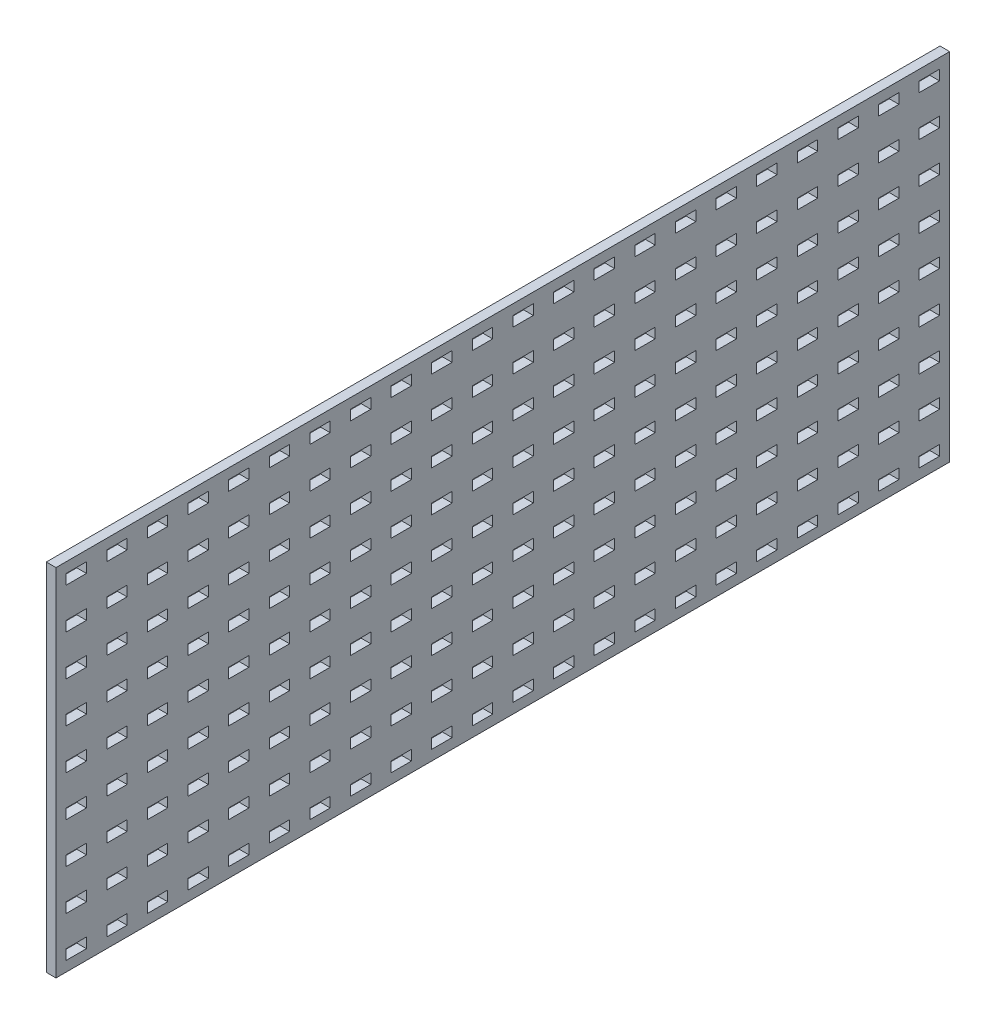
SolidWorks part; units mm, degrees
ref_plane "Front Plane" through (0, 0, 0) normal (0, 0, 1) x (1, 0, 0)
ref_plane "Top Plane" through (0, 0, 0) normal (0, 1, 0) x (1, 0, 0)
ref_plane "Right Plane" through (0, 0, 0) normal (1, 0, 0) x (0, 0, -1)
sketch "Sketch1" plane through (0, 0, 0) normal (1, 0, 0) x (0, 0, -1)
  line L1 (-279.4, -111.125) -> (279.4, -111.125)
  line L2 (-279.4, -111.125) -> (-279.4, 111.125)
  line L3 (-279.4, 111.125) -> (279.4, 111.125)
  line L4 (279.4, -111.125) -> (279.4, 111.125)
  line L5 (-279.4, -111.125) -> (279.4, 111.125) construction
  line L6 (-279.4, 111.125) -> (279.4, -111.125) construction
  point P0 (0, 0)
  dimension "D1" = 558.8
  dimension "D2" = 222.25
extrude "Boss-Extrude1" add sketch "Sketch1" along normal mid plane 6.0452
sketch "Sketch2" plane through (3.0226, 0, 0) normal (1, 0, 0) x (0, 0, -1)
  line L0 (-279.4, -111.125) -> (279.4, -111.125) construction
  line L1 (260.35, -98.425) -> (273.05, -98.425)
  line L2 (260.35, -98.425) -> (260.35, -104.775)
  line L3 (260.35, -104.775) -> (273.05, -104.775)
  line L4 (273.05, -98.425) -> (273.05, -104.775)
  line L5 (260.35, -98.425) -> (273.05, -104.775) construction
  line L6 (260.35, -104.775) -> (273.05, -98.425) construction
  line L7 (279.4, -111.125) -> (279.4, 111.125) construction
  line L8 (234.95, -104.775) -> (247.65, -104.775)
  line L9 (234.95, -98.425) -> (234.95, -104.775)
  line L10 (234.95, -98.425) -> (247.65, -98.425)
  line L11 (247.65, -98.425) -> (247.65, -104.775)
  line L12 (209.55, -104.775) -> (222.25, -104.775)
  line L13 (209.55, -98.425) -> (209.55, -104.775)
  line L14 (209.55, -98.425) -> (222.25, -98.425)
  line L15 (222.25, -98.425) -> (222.25, -104.775)
  line L16 (184.15, -104.775) -> (196.85, -104.775)
  line L17 (184.15, -98.425) -> (184.15, -104.775)
  line L18 (184.15, -98.425) -> (196.85, -98.425)
  line L19 (196.85, -98.425) -> (196.85, -104.775)
  line L20 (158.75, -104.775) -> (171.45, -104.775)
  line L21 (158.75, -98.425) -> (158.75, -104.775)
  line L22 (158.75, -98.425) -> (171.45, -98.425)
  line L23 (171.45, -98.425) -> (171.45, -104.775)
  line L24 (133.35, -104.775) -> (146.05, -104.775)
  line L25 (133.35, -98.425) -> (133.35, -104.775)
  line L26 (133.35, -98.425) -> (146.05, -98.425)
  line L27 (146.05, -98.425) -> (146.05, -104.775)
  line L28 (107.95, -104.775) -> (120.65, -104.775)
  line L29 (107.95, -98.425) -> (107.95, -104.775)
  line L30 (107.95, -98.425) -> (120.65, -98.425)
  line L31 (120.65, -98.425) -> (120.65, -104.775)
  line L32 (82.55, -104.775) -> (95.25, -104.775)
  line L33 (82.55, -98.425) -> (82.55, -104.775)
  line L34 (82.55, -98.425) -> (95.25, -98.425)
  line L35 (95.25, -98.425) -> (95.25, -104.775)
  line L36 (57.15, -104.775) -> (69.85, -104.775)
  line L37 (57.15, -98.425) -> (57.15, -104.775)
  line L38 (57.15, -98.425) -> (69.85, -98.425)
  line L39 (69.85, -98.425) -> (69.85, -104.775)
  line L40 (31.75, -104.775) -> (44.45, -104.775)
  line L41 (31.75, -98.425) -> (31.75, -104.775)
  line L42 (31.75, -98.425) -> (44.45, -98.425)
  line L43 (44.45, -98.425) -> (44.45, -104.775)
  line L44 (6.35, -104.775) -> (19.05, -104.775)
  line L45 (6.35, -98.425) -> (6.35, -104.775)
  line L46 (6.35, -98.425) -> (19.05, -98.425)
  line L47 (19.05, -98.425) -> (19.05, -104.775)
  line L48 (-19.05, -104.775) -> (-6.35, -104.775)
  line L49 (-19.05, -98.425) -> (-19.05, -104.775)
  line L50 (-19.05, -98.425) -> (-6.35, -98.425)
  line L51 (-6.35, -98.425) -> (-6.35, -104.775)
  line L52 (-44.45, -104.775) -> (-31.75, -104.775)
  line L53 (-44.45, -98.425) -> (-44.45, -104.775)
  line L54 (-44.45, -98.425) -> (-31.75, -98.425)
  line L55 (-31.75, -98.425) -> (-31.75, -104.775)
  line L56 (-69.85, -104.775) -> (-57.15, -104.775)
  line L57 (-69.85, -98.425) -> (-69.85, -104.775)
  line L58 (-69.85, -98.425) -> (-57.15, -98.425)
  line L59 (-57.15, -98.425) -> (-57.15, -104.775)
  line L60 (-95.25, -104.775) -> (-82.55, -104.775)
  line L61 (-95.25, -98.425) -> (-95.25, -104.775)
  line L62 (-95.25, -98.425) -> (-82.55, -98.425)
  line L63 (-82.55, -98.425) -> (-82.55, -104.775)
  line L64 (-120.65, -104.775) -> (-107.95, -104.775)
  line L65 (-120.65, -98.425) -> (-120.65, -104.775)
  line L66 (-120.65, -98.425) -> (-107.95, -98.425)
  line L67 (-107.95, -98.425) -> (-107.95, -104.775)
  line L68 (-146.05, -104.775) -> (-133.35, -104.775)
  line L69 (-146.05, -98.425) -> (-146.05, -104.775)
  line L70 (-146.05, -98.425) -> (-133.35, -98.425)
  line L71 (-133.35, -98.425) -> (-133.35, -104.775)
  line L72 (-171.45, -104.775) -> (-158.75, -104.775)
  line L73 (-171.45, -98.425) -> (-171.45, -104.775)
  line L74 (-171.45, -98.425) -> (-158.75, -98.425)
  line L75 (-158.75, -98.425) -> (-158.75, -104.775)
  line L76 (-196.85, -104.775) -> (-184.15, -104.775)
  line L77 (-196.85, -98.425) -> (-196.85, -104.775)
  line L78 (-196.85, -98.425) -> (-184.15, -98.425)
  line L79 (-184.15, -98.425) -> (-184.15, -104.775)
  line L80 (-222.25, -104.775) -> (-209.55, -104.775)
  line L81 (-222.25, -98.425) -> (-222.25, -104.775)
  line L82 (-222.25, -98.425) -> (-209.55, -98.425)
  line L83 (-209.55, -98.425) -> (-209.55, -104.775)
  line L84 (-247.65, -104.775) -> (-234.95, -104.775)
  line L85 (-247.65, -98.425) -> (-247.65, -104.775)
  line L86 (-247.65, -98.425) -> (-234.95, -98.425)
  line L87 (-234.95, -98.425) -> (-234.95, -104.775)
  line L88 (-273.05, -104.775) -> (-260.35, -104.775)
  line L89 (-273.05, -98.425) -> (-273.05, -104.775)
  line L90 (-273.05, -98.425) -> (-260.35, -98.425)
  line L91 (-260.35, -98.425) -> (-260.35, -104.775)
  line L92 (234.95, -79.375) -> (247.65, -79.375)
  line L93 (234.95, -73.025) -> (234.95, -79.375)
  line L94 (234.95, -73.025) -> (247.65, -73.025)
  line L95 (247.65, -73.025) -> (247.65, -79.375)
  line L96 (209.55, -79.375) -> (222.25, -79.375)
  line L97 (209.55, -73.025) -> (209.55, -79.375)
  line L98 (209.55, -73.025) -> (222.25, -73.025)
  line L99 (222.25, -73.025) -> (222.25, -79.375)
  line L100 (184.15, -79.375) -> (196.85, -79.375)
  line L101 (184.15, -73.025) -> (184.15, -79.375)
  line L102 (184.15, -73.025) -> (196.85, -73.025)
  line L103 (196.85, -73.025) -> (196.85, -79.375)
  line L104 (158.75, -79.375) -> (171.45, -79.375)
  line L105 (158.75, -73.025) -> (158.75, -79.375)
  line L106 (158.75, -73.025) -> (171.45, -73.025)
  line L107 (171.45, -73.025) -> (171.45, -79.375)
  line L108 (133.35, -79.375) -> (146.05, -79.375)
  line L109 (133.35, -73.025) -> (133.35, -79.375)
  line L110 (133.35, -73.025) -> (146.05, -73.025)
  line L111 (146.05, -73.025) -> (146.05, -79.375)
  line L112 (107.95, -79.375) -> (120.65, -79.375)
  line L113 (107.95, -73.025) -> (107.95, -79.375)
  line L114 (107.95, -73.025) -> (120.65, -73.025)
  line L115 (120.65, -73.025) -> (120.65, -79.375)
  line L116 (82.55, -79.375) -> (95.25, -79.375)
  line L117 (82.55, -73.025) -> (82.55, -79.375)
  line L118 (82.55, -73.025) -> (95.25, -73.025)
  line L119 (95.25, -73.025) -> (95.25, -79.375)
  line L120 (57.15, -79.375) -> (69.85, -79.375)
  line L121 (57.15, -73.025) -> (57.15, -79.375)
  line L122 (57.15, -73.025) -> (69.85, -73.025)
  line L123 (69.85, -73.025) -> (69.85, -79.375)
  line L124 (31.75, -79.375) -> (44.45, -79.375)
  line L125 (31.75, -73.025) -> (31.75, -79.375)
  line L126 (31.75, -73.025) -> (44.45, -73.025)
  line L127 (44.45, -73.025) -> (44.45, -79.375)
  line L128 (6.35, -79.375) -> (19.05, -79.375)
  line L129 (6.35, -73.025) -> (6.35, -79.375)
  line L130 (6.35, -73.025) -> (19.05, -73.025)
  line L131 (19.05, -73.025) -> (19.05, -79.375)
  line L132 (-19.05, -79.375) -> (-6.35, -79.375)
  line L133 (-19.05, -73.025) -> (-19.05, -79.375)
  line L134 (-19.05, -73.025) -> (-6.35, -73.025)
  line L135 (-6.35, -73.025) -> (-6.35, -79.375)
  line L136 (-44.45, -79.375) -> (-31.75, -79.375)
  line L137 (-44.45, -73.025) -> (-44.45, -79.375)
  line L138 (-44.45, -73.025) -> (-31.75, -73.025)
  line L139 (-31.75, -73.025) -> (-31.75, -79.375)
  line L140 (-69.85, -79.375) -> (-57.15, -79.375)
  line L141 (-69.85, -73.025) -> (-69.85, -79.375)
  line L142 (-69.85, -73.025) -> (-57.15, -73.025)
  line L143 (-57.15, -73.025) -> (-57.15, -79.375)
  line L144 (-95.25, -79.375) -> (-82.55, -79.375)
  line L145 (-95.25, -73.025) -> (-95.25, -79.375)
  line L146 (-95.25, -73.025) -> (-82.55, -73.025)
  line L147 (-82.55, -73.025) -> (-82.55, -79.375)
  line L148 (-120.65, -79.375) -> (-107.95, -79.375)
  line L149 (-120.65, -73.025) -> (-120.65, -79.375)
  line L150 (-120.65, -73.025) -> (-107.95, -73.025)
  line L151 (-107.95, -73.025) -> (-107.95, -79.375)
  line L152 (-146.05, -79.375) -> (-133.35, -79.375)
  line L153 (-146.05, -73.025) -> (-146.05, -79.375)
  line L154 (-146.05, -73.025) -> (-133.35, -73.025)
  line L155 (-133.35, -73.025) -> (-133.35, -79.375)
  line L156 (-171.45, -79.375) -> (-158.75, -79.375)
  line L157 (-171.45, -73.025) -> (-171.45, -79.375)
  line L158 (-171.45, -73.025) -> (-158.75, -73.025)
  line L159 (-158.75, -73.025) -> (-158.75, -79.375)
  line L160 (-196.85, -79.375) -> (-184.15, -79.375)
  line L161 (-196.85, -73.025) -> (-196.85, -79.375)
  line L162 (-196.85, -73.025) -> (-184.15, -73.025)
  line L163 (-184.15, -73.025) -> (-184.15, -79.375)
  line L164 (-222.25, -79.375) -> (-209.55, -79.375)
  line L165 (-222.25, -73.025) -> (-222.25, -79.375)
  line L166 (-222.25, -73.025) -> (-209.55, -73.025)
  line L167 (-209.55, -73.025) -> (-209.55, -79.375)
  line L168 (-247.65, -79.375) -> (-234.95, -79.375)
  line L169 (-247.65, -73.025) -> (-247.65, -79.375)
  line L170 (-247.65, -73.025) -> (-234.95, -73.025)
  line L171 (-234.95, -73.025) -> (-234.95, -79.375)
  line L172 (-273.05, -79.375) -> (-260.35, -79.375)
  line L173 (-273.05, -73.025) -> (-273.05, -79.375)
  line L174 (-273.05, -73.025) -> (-260.35, -73.025)
  line L175 (-260.35, -73.025) -> (-260.35, -79.375)
  line L176 (234.95, -53.975) -> (247.65, -53.975)
  line L177 (234.95, -47.625) -> (234.95, -53.975)
  line L178 (234.95, -47.625) -> (247.65, -47.625)
  line L179 (247.65, -47.625) -> (247.65, -53.975)
  line L180 (209.55, -53.975) -> (222.25, -53.975)
  line L181 (209.55, -47.625) -> (209.55, -53.975)
  line L182 (209.55, -47.625) -> (222.25, -47.625)
  line L183 (222.25, -47.625) -> (222.25, -53.975)
  line L184 (184.15, -53.975) -> (196.85, -53.975)
  line L185 (184.15, -47.625) -> (184.15, -53.975)
  line L186 (184.15, -47.625) -> (196.85, -47.625)
  line L187 (196.85, -47.625) -> (196.85, -53.975)
  line L188 (158.75, -53.975) -> (171.45, -53.975)
  line L189 (158.75, -47.625) -> (158.75, -53.975)
  line L190 (158.75, -47.625) -> (171.45, -47.625)
  line L191 (171.45, -47.625) -> (171.45, -53.975)
  line L192 (133.35, -53.975) -> (146.05, -53.975)
  line L193 (133.35, -47.625) -> (133.35, -53.975)
  line L194 (133.35, -47.625) -> (146.05, -47.625)
  line L195 (146.05, -47.625) -> (146.05, -53.975)
  line L196 (107.95, -53.975) -> (120.65, -53.975)
  line L197 (107.95, -47.625) -> (107.95, -53.975)
  line L198 (107.95, -47.625) -> (120.65, -47.625)
  line L199 (120.65, -47.625) -> (120.65, -53.975)
  line L200 (82.55, -53.975) -> (95.25, -53.975)
  line L201 (82.55, -47.625) -> (82.55, -53.975)
  line L202 (82.55, -47.625) -> (95.25, -47.625)
  line L203 (95.25, -47.625) -> (95.25, -53.975)
  line L204 (57.15, -53.975) -> (69.85, -53.975)
  line L205 (57.15, -47.625) -> (57.15, -53.975)
  line L206 (57.15, -47.625) -> (69.85, -47.625)
  line L207 (69.85, -47.625) -> (69.85, -53.975)
  line L208 (31.75, -53.975) -> (44.45, -53.975)
  line L209 (31.75, -47.625) -> (31.75, -53.975)
  line L210 (31.75, -47.625) -> (44.45, -47.625)
  line L211 (44.45, -47.625) -> (44.45, -53.975)
  line L212 (6.35, -53.975) -> (19.05, -53.975)
  line L213 (6.35, -47.625) -> (6.35, -53.975)
  line L214 (6.35, -47.625) -> (19.05, -47.625)
  line L215 (19.05, -47.625) -> (19.05, -53.975)
  line L216 (-19.05, -53.975) -> (-6.35, -53.975)
  line L217 (-19.05, -47.625) -> (-19.05, -53.975)
  line L218 (-19.05, -47.625) -> (-6.35, -47.625)
  line L219 (-6.35, -47.625) -> (-6.35, -53.975)
  line L220 (-44.45, -53.975) -> (-31.75, -53.975)
  line L221 (-44.45, -47.625) -> (-44.45, -53.975)
  line L222 (-44.45, -47.625) -> (-31.75, -47.625)
  line L223 (-31.75, -47.625) -> (-31.75, -53.975)
  line L224 (-69.85, -53.975) -> (-57.15, -53.975)
  line L225 (-69.85, -47.625) -> (-69.85, -53.975)
  line L226 (-69.85, -47.625) -> (-57.15, -47.625)
  line L227 (-57.15, -47.625) -> (-57.15, -53.975)
  line L228 (-95.25, -53.975) -> (-82.55, -53.975)
  line L229 (-95.25, -47.625) -> (-95.25, -53.975)
  line L230 (-95.25, -47.625) -> (-82.55, -47.625)
  line L231 (-82.55, -47.625) -> (-82.55, -53.975)
  line L232 (-120.65, -53.975) -> (-107.95, -53.975)
  line L233 (-120.65, -47.625) -> (-120.65, -53.975)
  line L234 (-120.65, -47.625) -> (-107.95, -47.625)
  line L235 (-107.95, -47.625) -> (-107.95, -53.975)
  line L236 (-146.05, -53.975) -> (-133.35, -53.975)
  line L237 (-146.05, -47.625) -> (-146.05, -53.975)
  line L238 (-146.05, -47.625) -> (-133.35, -47.625)
  line L239 (-133.35, -47.625) -> (-133.35, -53.975)
  line L240 (-171.45, -53.975) -> (-158.75, -53.975)
  line L241 (-171.45, -47.625) -> (-171.45, -53.975)
  line L242 (-171.45, -47.625) -> (-158.75, -47.625)
  line L243 (-158.75, -47.625) -> (-158.75, -53.975)
  line L244 (-196.85, -53.975) -> (-184.15, -53.975)
  line L245 (-196.85, -47.625) -> (-196.85, -53.975)
  line L246 (-196.85, -47.625) -> (-184.15, -47.625)
  line L247 (-184.15, -47.625) -> (-184.15, -53.975)
  line L248 (-222.25, -53.975) -> (-209.55, -53.975)
  line L249 (-222.25, -47.625) -> (-222.25, -53.975)
  line L250 (-222.25, -47.625) -> (-209.55, -47.625)
  line L251 (-209.55, -47.625) -> (-209.55, -53.975)
  line L252 (-247.65, -53.975) -> (-234.95, -53.975)
  line L253 (-247.65, -47.625) -> (-247.65, -53.975)
  line L254 (-247.65, -47.625) -> (-234.95, -47.625)
  line L255 (-234.95, -47.625) -> (-234.95, -53.975)
  line L256 (-273.05, -53.975) -> (-260.35, -53.975)
  line L257 (-273.05, -47.625) -> (-273.05, -53.975)
  line L258 (-273.05, -47.625) -> (-260.35, -47.625)
  line L259 (-260.35, -47.625) -> (-260.35, -53.975)
  line L260 (234.95, -28.575) -> (247.65, -28.575)
  line L261 (234.95, -22.225) -> (234.95, -28.575)
  line L262 (234.95, -22.225) -> (247.65, -22.225)
  line L263 (247.65, -22.225) -> (247.65, -28.575)
  line L264 (209.55, -28.575) -> (222.25, -28.575)
  line L265 (209.55, -22.225) -> (209.55, -28.575)
  line L266 (209.55, -22.225) -> (222.25, -22.225)
  line L267 (222.25, -22.225) -> (222.25, -28.575)
  line L268 (184.15, -28.575) -> (196.85, -28.575)
  line L269 (184.15, -22.225) -> (184.15, -28.575)
  line L270 (184.15, -22.225) -> (196.85, -22.225)
  line L271 (196.85, -22.225) -> (196.85, -28.575)
  line L272 (158.75, -28.575) -> (171.45, -28.575)
  line L273 (158.75, -22.225) -> (158.75, -28.575)
  line L274 (158.75, -22.225) -> (171.45, -22.225)
  line L275 (171.45, -22.225) -> (171.45, -28.575)
  line L276 (133.35, -28.575) -> (146.05, -28.575)
  line L277 (133.35, -22.225) -> (133.35, -28.575)
  line L278 (133.35, -22.225) -> (146.05, -22.225)
  line L279 (146.05, -22.225) -> (146.05, -28.575)
  line L280 (107.95, -28.575) -> (120.65, -28.575)
  line L281 (107.95, -22.225) -> (107.95, -28.575)
  line L282 (107.95, -22.225) -> (120.65, -22.225)
  line L283 (120.65, -22.225) -> (120.65, -28.575)
  line L284 (82.55, -28.575) -> (95.25, -28.575)
  line L285 (82.55, -22.225) -> (82.55, -28.575)
  line L286 (82.55, -22.225) -> (95.25, -22.225)
  line L287 (95.25, -22.225) -> (95.25, -28.575)
  line L288 (57.15, -28.575) -> (69.85, -28.575)
  line L289 (57.15, -22.225) -> (57.15, -28.575)
  line L290 (57.15, -22.225) -> (69.85, -22.225)
  line L291 (69.85, -22.225) -> (69.85, -28.575)
  line L292 (31.75, -28.575) -> (44.45, -28.575)
  line L293 (31.75, -22.225) -> (31.75, -28.575)
  line L294 (31.75, -22.225) -> (44.45, -22.225)
  line L295 (44.45, -22.225) -> (44.45, -28.575)
  line L296 (6.35, -28.575) -> (19.05, -28.575)
  line L297 (6.35, -22.225) -> (6.35, -28.575)
  line L298 (6.35, -22.225) -> (19.05, -22.225)
  line L299 (19.05, -22.225) -> (19.05, -28.575)
  line L300 (-19.05, -28.575) -> (-6.35, -28.575)
  line L301 (-19.05, -22.225) -> (-19.05, -28.575)
  line L302 (-19.05, -22.225) -> (-6.35, -22.225)
  line L303 (-6.35, -22.225) -> (-6.35, -28.575)
  line L304 (-44.45, -28.575) -> (-31.75, -28.575)
  line L305 (-44.45, -22.225) -> (-44.45, -28.575)
  line L306 (-44.45, -22.225) -> (-31.75, -22.225)
  line L307 (-31.75, -22.225) -> (-31.75, -28.575)
  line L308 (-69.85, -28.575) -> (-57.15, -28.575)
  line L309 (-69.85, -22.225) -> (-69.85, -28.575)
  line L310 (-69.85, -22.225) -> (-57.15, -22.225)
  line L311 (-57.15, -22.225) -> (-57.15, -28.575)
  line L312 (-95.25, -28.575) -> (-82.55, -28.575)
  line L313 (-95.25, -22.225) -> (-95.25, -28.575)
  line L314 (-95.25, -22.225) -> (-82.55, -22.225)
  line L315 (-82.55, -22.225) -> (-82.55, -28.575)
  line L316 (-120.65, -28.575) -> (-107.95, -28.575)
  line L317 (-120.65, -22.225) -> (-120.65, -28.575)
  line L318 (-120.65, -22.225) -> (-107.95, -22.225)
  line L319 (-107.95, -22.225) -> (-107.95, -28.575)
  line L320 (-146.05, -28.575) -> (-133.35, -28.575)
  line L321 (-146.05, -22.225) -> (-146.05, -28.575)
  line L322 (-146.05, -22.225) -> (-133.35, -22.225)
  line L323 (-133.35, -22.225) -> (-133.35, -28.575)
  line L324 (-171.45, -28.575) -> (-158.75, -28.575)
  line L325 (-171.45, -22.225) -> (-171.45, -28.575)
  line L326 (-171.45, -22.225) -> (-158.75, -22.225)
  line L327 (-158.75, -22.225) -> (-158.75, -28.575)
  line L328 (-196.85, -28.575) -> (-184.15, -28.575)
  line L329 (-196.85, -22.225) -> (-196.85, -28.575)
  line L330 (-196.85, -22.225) -> (-184.15, -22.225)
  line L331 (-184.15, -22.225) -> (-184.15, -28.575)
  line L332 (-222.25, -28.575) -> (-209.55, -28.575)
  line L333 (-222.25, -22.225) -> (-222.25, -28.575)
  line L334 (-222.25, -22.225) -> (-209.55, -22.225)
  line L335 (-209.55, -22.225) -> (-209.55, -28.575)
  line L336 (-247.65, -28.575) -> (-234.95, -28.575)
  line L337 (-247.65, -22.225) -> (-247.65, -28.575)
  line L338 (-247.65, -22.225) -> (-234.95, -22.225)
  line L339 (-234.95, -22.225) -> (-234.95, -28.575)
  line L340 (-273.05, -28.575) -> (-260.35, -28.575)
  line L341 (-273.05, -22.225) -> (-273.05, -28.575)
  line L342 (-273.05, -22.225) -> (-260.35, -22.225)
  line L343 (-260.35, -22.225) -> (-260.35, -28.575)
  line L344 (234.95, -3.175) -> (247.65, -3.175)
  line L345 (234.95, 3.175) -> (234.95, -3.175)
  line L346 (234.95, 3.175) -> (247.65, 3.175)
  line L347 (247.65, 3.175) -> (247.65, -3.175)
  line L348 (209.55, -3.175) -> (222.25, -3.175)
  line L349 (209.55, 3.175) -> (209.55, -3.175)
  line L350 (209.55, 3.175) -> (222.25, 3.175)
  line L351 (222.25, 3.175) -> (222.25, -3.175)
  line L352 (184.15, -3.175) -> (196.85, -3.175)
  line L353 (184.15, 3.175) -> (184.15, -3.175)
  line L354 (184.15, 3.175) -> (196.85, 3.175)
  line L355 (196.85, 3.175) -> (196.85, -3.175)
  line L356 (158.75, -3.175) -> (171.45, -3.175)
  line L357 (158.75, 3.175) -> (158.75, -3.175)
  line L358 (158.75, 3.175) -> (171.45, 3.175)
  line L359 (171.45, 3.175) -> (171.45, -3.175)
  line L360 (133.35, -3.175) -> (146.05, -3.175)
  line L361 (133.35, 3.175) -> (133.35, -3.175)
  line L362 (133.35, 3.175) -> (146.05, 3.175)
  line L363 (146.05, 3.175) -> (146.05, -3.175)
  line L364 (107.95, -3.175) -> (120.65, -3.175)
  line L365 (107.95, 3.175) -> (107.95, -3.175)
  line L366 (107.95, 3.175) -> (120.65, 3.175)
  line L367 (120.65, 3.175) -> (120.65, -3.175)
  line L368 (82.55, -3.175) -> (95.25, -3.175)
  line L369 (82.55, 3.175) -> (82.55, -3.175)
  line L370 (82.55, 3.175) -> (95.25, 3.175)
  line L371 (95.25, 3.175) -> (95.25, -3.175)
  line L372 (57.15, -3.175) -> (69.85, -3.175)
  line L373 (57.15, 3.175) -> (57.15, -3.175)
  line L374 (57.15, 3.175) -> (69.85, 3.175)
  line L375 (69.85, 3.175) -> (69.85, -3.175)
  line L376 (31.75, -3.175) -> (44.45, -3.175)
  line L377 (31.75, 3.175) -> (31.75, -3.175)
  line L378 (31.75, 3.175) -> (44.45, 3.175)
  line L379 (44.45, 3.175) -> (44.45, -3.175)
  line L380 (6.35, -3.175) -> (19.05, -3.175)
  line L381 (6.35, 3.175) -> (6.35, -3.175)
  line L382 (6.35, 3.175) -> (19.05, 3.175)
  line L383 (19.05, 3.175) -> (19.05, -3.175)
  line L384 (-19.05, -3.175) -> (-6.35, -3.175)
  line L385 (-19.05, 3.175) -> (-19.05, -3.175)
  line L386 (-19.05, 3.175) -> (-6.35, 3.175)
  line L387 (-6.35, 3.175) -> (-6.35, -3.175)
  line L388 (-44.45, -3.175) -> (-31.75, -3.175)
  line L389 (-44.45, 3.175) -> (-44.45, -3.175)
  line L390 (-44.45, 3.175) -> (-31.75, 3.175)
  line L391 (-31.75, 3.175) -> (-31.75, -3.175)
  line L392 (-69.85, -3.175) -> (-57.15, -3.175)
  line L393 (-69.85, 3.175) -> (-69.85, -3.175)
  line L394 (-69.85, 3.175) -> (-57.15, 3.175)
  line L395 (-57.15, 3.175) -> (-57.15, -3.175)
  line L396 (-95.25, -3.175) -> (-82.55, -3.175)
  line L397 (-95.25, 3.175) -> (-95.25, -3.175)
  line L398 (-95.25, 3.175) -> (-82.55, 3.175)
  line L399 (-82.55, 3.175) -> (-82.55, -3.175)
  line L400 (-120.65, -3.175) -> (-107.95, -3.175)
  line L401 (-120.65, 3.175) -> (-120.65, -3.175)
  line L402 (-120.65, 3.175) -> (-107.95, 3.175)
  line L403 (-107.95, 3.175) -> (-107.95, -3.175)
  line L404 (-146.05, -3.175) -> (-133.35, -3.175)
  line L405 (-146.05, 3.175) -> (-146.05, -3.175)
  line L406 (-146.05, 3.175) -> (-133.35, 3.175)
  line L407 (-133.35, 3.175) -> (-133.35, -3.175)
  line L408 (-171.45, -3.175) -> (-158.75, -3.175)
  line L409 (-171.45, 3.175) -> (-171.45, -3.175)
  line L410 (-171.45, 3.175) -> (-158.75, 3.175)
  line L411 (-158.75, 3.175) -> (-158.75, -3.175)
  line L412 (-196.85, -3.175) -> (-184.15, -3.175)
  line L413 (-196.85, 3.175) -> (-196.85, -3.175)
  line L414 (-196.85, 3.175) -> (-184.15, 3.175)
  line L415 (-184.15, 3.175) -> (-184.15, -3.175)
  line L416 (-222.25, -3.175) -> (-209.55, -3.175)
  line L417 (-222.25, 3.175) -> (-222.25, -3.175)
  line L418 (-222.25, 3.175) -> (-209.55, 3.175)
  line L419 (-209.55, 3.175) -> (-209.55, -3.175)
  line L420 (-247.65, -3.175) -> (-234.95, -3.175)
  line L421 (-247.65, 3.175) -> (-247.65, -3.175)
  line L422 (-247.65, 3.175) -> (-234.95, 3.175)
  line L423 (-234.95, 3.175) -> (-234.95, -3.175)
  line L424 (-273.05, -3.175) -> (-260.35, -3.175)
  line L425 (-273.05, 3.175) -> (-273.05, -3.175)
  line L426 (-273.05, 3.175) -> (-260.35, 3.175)
  line L427 (-260.35, 3.175) -> (-260.35, -3.175)
  line L428 (234.95, 22.225) -> (247.65, 22.225)
  line L429 (234.95, 28.575) -> (234.95, 22.225)
  line L430 (234.95, 28.575) -> (247.65, 28.575)
  line L431 (247.65, 28.575) -> (247.65, 22.225)
  line L432 (209.55, 22.225) -> (222.25, 22.225)
  line L433 (209.55, 28.575) -> (209.55, 22.225)
  line L434 (209.55, 28.575) -> (222.25, 28.575)
  line L435 (222.25, 28.575) -> (222.25, 22.225)
  line L436 (184.15, 22.225) -> (196.85, 22.225)
  line L437 (184.15, 28.575) -> (184.15, 22.225)
  line L438 (184.15, 28.575) -> (196.85, 28.575)
  line L439 (196.85, 28.575) -> (196.85, 22.225)
  line L440 (158.75, 22.225) -> (171.45, 22.225)
  line L441 (158.75, 28.575) -> (158.75, 22.225)
  line L442 (158.75, 28.575) -> (171.45, 28.575)
  line L443 (171.45, 28.575) -> (171.45, 22.225)
  line L444 (133.35, 22.225) -> (146.05, 22.225)
  line L445 (133.35, 28.575) -> (133.35, 22.225)
  line L446 (133.35, 28.575) -> (146.05, 28.575)
  line L447 (146.05, 28.575) -> (146.05, 22.225)
  line L448 (107.95, 22.225) -> (120.65, 22.225)
  line L449 (107.95, 28.575) -> (107.95, 22.225)
  line L450 (107.95, 28.575) -> (120.65, 28.575)
  line L451 (120.65, 28.575) -> (120.65, 22.225)
  line L452 (82.55, 22.225) -> (95.25, 22.225)
  line L453 (82.55, 28.575) -> (82.55, 22.225)
  line L454 (82.55, 28.575) -> (95.25, 28.575)
  line L455 (95.25, 28.575) -> (95.25, 22.225)
  line L456 (57.15, 22.225) -> (69.85, 22.225)
  line L457 (57.15, 28.575) -> (57.15, 22.225)
  line L458 (57.15, 28.575) -> (69.85, 28.575)
  line L459 (69.85, 28.575) -> (69.85, 22.225)
  line L460 (31.75, 22.225) -> (44.45, 22.225)
  line L461 (31.75, 28.575) -> (31.75, 22.225)
  line L462 (31.75, 28.575) -> (44.45, 28.575)
  line L463 (44.45, 28.575) -> (44.45, 22.225)
  line L464 (6.35, 22.225) -> (19.05, 22.225)
  line L465 (6.35, 28.575) -> (6.35, 22.225)
  line L466 (6.35, 28.575) -> (19.05, 28.575)
  line L467 (19.05, 28.575) -> (19.05, 22.225)
  line L468 (-19.05, 22.225) -> (-6.35, 22.225)
  line L469 (-19.05, 28.575) -> (-19.05, 22.225)
  line L470 (-19.05, 28.575) -> (-6.35, 28.575)
  line L471 (-6.35, 28.575) -> (-6.35, 22.225)
  line L472 (-44.45, 22.225) -> (-31.75, 22.225)
  line L473 (-44.45, 28.575) -> (-44.45, 22.225)
  line L474 (-44.45, 28.575) -> (-31.75, 28.575)
  line L475 (-31.75, 28.575) -> (-31.75, 22.225)
  line L476 (-69.85, 22.225) -> (-57.15, 22.225)
  line L477 (-69.85, 28.575) -> (-69.85, 22.225)
  line L478 (-69.85, 28.575) -> (-57.15, 28.575)
  line L479 (-57.15, 28.575) -> (-57.15, 22.225)
  line L480 (-95.25, 22.225) -> (-82.55, 22.225)
  line L481 (-95.25, 28.575) -> (-95.25, 22.225)
  line L482 (-95.25, 28.575) -> (-82.55, 28.575)
  line L483 (-82.55, 28.575) -> (-82.55, 22.225)
  line L484 (-120.65, 22.225) -> (-107.95, 22.225)
  line L485 (-120.65, 28.575) -> (-120.65, 22.225)
  line L486 (-120.65, 28.575) -> (-107.95, 28.575)
  line L487 (-107.95, 28.575) -> (-107.95, 22.225)
  line L488 (-146.05, 22.225) -> (-133.35, 22.225)
  line L489 (-146.05, 28.575) -> (-146.05, 22.225)
  line L490 (-146.05, 28.575) -> (-133.35, 28.575)
  line L491 (-133.35, 28.575) -> (-133.35, 22.225)
  line L492 (-171.45, 22.225) -> (-158.75, 22.225)
  line L493 (-171.45, 28.575) -> (-171.45, 22.225)
  line L494 (-171.45, 28.575) -> (-158.75, 28.575)
  line L495 (-158.75, 28.575) -> (-158.75, 22.225)
  line L496 (-196.85, 22.225) -> (-184.15, 22.225)
  line L497 (-196.85, 28.575) -> (-196.85, 22.225)
  line L498 (-196.85, 28.575) -> (-184.15, 28.575)
  line L499 (-184.15, 28.575) -> (-184.15, 22.225)
  line L500 (-222.25, 22.225) -> (-209.55, 22.225)
  line L501 (-222.25, 28.575) -> (-222.25, 22.225)
  line L502 (-222.25, 28.575) -> (-209.55, 28.575)
  line L503 (-209.55, 28.575) -> (-209.55, 22.225)
  line L504 (-247.65, 22.225) -> (-234.95, 22.225)
  line L505 (-247.65, 28.575) -> (-247.65, 22.225)
  line L506 (-247.65, 28.575) -> (-234.95, 28.575)
  line L507 (-234.95, 28.575) -> (-234.95, 22.225)
  line L508 (-273.05, 22.225) -> (-260.35, 22.225)
  line L509 (-273.05, 28.575) -> (-273.05, 22.225)
  line L510 (-273.05, 28.575) -> (-260.35, 28.575)
  line L511 (-260.35, 28.575) -> (-260.35, 22.225)
  line L512 (234.95, 47.625) -> (247.65, 47.625)
  line L513 (234.95, 53.975) -> (234.95, 47.625)
  line L514 (234.95, 53.975) -> (247.65, 53.975)
  line L515 (247.65, 53.975) -> (247.65, 47.625)
  line L516 (209.55, 47.625) -> (222.25, 47.625)
  line L517 (209.55, 53.975) -> (209.55, 47.625)
  line L518 (209.55, 53.975) -> (222.25, 53.975)
  line L519 (222.25, 53.975) -> (222.25, 47.625)
  line L520 (184.15, 47.625) -> (196.85, 47.625)
  line L521 (184.15, 53.975) -> (184.15, 47.625)
  line L522 (184.15, 53.975) -> (196.85, 53.975)
  line L523 (196.85, 53.975) -> (196.85, 47.625)
  line L524 (158.75, 47.625) -> (171.45, 47.625)
  line L525 (158.75, 53.975) -> (158.75, 47.625)
  line L526 (158.75, 53.975) -> (171.45, 53.975)
  line L527 (171.45, 53.975) -> (171.45, 47.625)
  line L528 (133.35, 47.625) -> (146.05, 47.625)
  line L529 (133.35, 53.975) -> (133.35, 47.625)
  line L530 (133.35, 53.975) -> (146.05, 53.975)
  line L531 (146.05, 53.975) -> (146.05, 47.625)
  line L532 (107.95, 47.625) -> (120.65, 47.625)
  line L533 (107.95, 53.975) -> (107.95, 47.625)
  line L534 (107.95, 53.975) -> (120.65, 53.975)
  line L535 (120.65, 53.975) -> (120.65, 47.625)
  line L536 (82.55, 47.625) -> (95.25, 47.625)
  line L537 (82.55, 53.975) -> (82.55, 47.625)
  line L538 (82.55, 53.975) -> (95.25, 53.975)
  line L539 (95.25, 53.975) -> (95.25, 47.625)
  line L540 (57.15, 47.625) -> (69.85, 47.625)
  line L541 (57.15, 53.975) -> (57.15, 47.625)
  line L542 (57.15, 53.975) -> (69.85, 53.975)
  line L543 (69.85, 53.975) -> (69.85, 47.625)
  line L544 (31.75, 47.625) -> (44.45, 47.625)
  line L545 (31.75, 53.975) -> (31.75, 47.625)
  line L546 (31.75, 53.975) -> (44.45, 53.975)
  line L547 (44.45, 53.975) -> (44.45, 47.625)
  line L548 (6.35, 47.625) -> (19.05, 47.625)
  line L549 (6.35, 53.975) -> (6.35, 47.625)
  line L550 (6.35, 53.975) -> (19.05, 53.975)
  line L551 (19.05, 53.975) -> (19.05, 47.625)
  line L552 (-19.05, 47.625) -> (-6.35, 47.625)
  line L553 (-19.05, 53.975) -> (-19.05, 47.625)
  line L554 (-19.05, 53.975) -> (-6.35, 53.975)
  line L555 (-6.35, 53.975) -> (-6.35, 47.625)
  line L556 (-44.45, 47.625) -> (-31.75, 47.625)
  line L557 (-44.45, 53.975) -> (-44.45, 47.625)
  line L558 (-44.45, 53.975) -> (-31.75, 53.975)
  line L559 (-31.75, 53.975) -> (-31.75, 47.625)
  line L560 (-69.85, 47.625) -> (-57.15, 47.625)
  line L561 (-69.85, 53.975) -> (-69.85, 47.625)
  line L562 (-69.85, 53.975) -> (-57.15, 53.975)
  line L563 (-57.15, 53.975) -> (-57.15, 47.625)
  line L564 (-95.25, 47.625) -> (-82.55, 47.625)
  line L565 (-95.25, 53.975) -> (-95.25, 47.625)
  line L566 (-95.25, 53.975) -> (-82.55, 53.975)
  line L567 (-82.55, 53.975) -> (-82.55, 47.625)
  line L568 (-120.65, 47.625) -> (-107.95, 47.625)
  line L569 (-120.65, 53.975) -> (-120.65, 47.625)
  line L570 (-120.65, 53.975) -> (-107.95, 53.975)
  line L571 (-107.95, 53.975) -> (-107.95, 47.625)
  line L572 (-146.05, 47.625) -> (-133.35, 47.625)
  line L573 (-146.05, 53.975) -> (-146.05, 47.625)
  line L574 (-146.05, 53.975) -> (-133.35, 53.975)
  line L575 (-133.35, 53.975) -> (-133.35, 47.625)
  line L576 (-171.45, 47.625) -> (-158.75, 47.625)
  line L577 (-171.45, 53.975) -> (-171.45, 47.625)
  line L578 (-171.45, 53.975) -> (-158.75, 53.975)
  line L579 (-158.75, 53.975) -> (-158.75, 47.625)
  line L580 (-196.85, 47.625) -> (-184.15, 47.625)
  line L581 (-196.85, 53.975) -> (-196.85, 47.625)
  line L582 (-196.85, 53.975) -> (-184.15, 53.975)
  line L583 (-184.15, 53.975) -> (-184.15, 47.625)
  line L584 (-222.25, 47.625) -> (-209.55, 47.625)
  line L585 (-222.25, 53.975) -> (-222.25, 47.625)
  line L586 (-222.25, 53.975) -> (-209.55, 53.975)
  line L587 (-209.55, 53.975) -> (-209.55, 47.625)
  line L588 (-247.65, 47.625) -> (-234.95, 47.625)
  line L589 (-247.65, 53.975) -> (-247.65, 47.625)
  line L590 (-247.65, 53.975) -> (-234.95, 53.975)
  line L591 (-234.95, 53.975) -> (-234.95, 47.625)
  line L592 (-273.05, 47.625) -> (-260.35, 47.625)
  line L593 (-273.05, 53.975) -> (-273.05, 47.625)
  line L594 (-273.05, 53.975) -> (-260.35, 53.975)
  line L595 (-260.35, 53.975) -> (-260.35, 47.625)
  line L596 (234.95, 73.025) -> (247.65, 73.025)
  line L597 (234.95, 79.375) -> (234.95, 73.025)
  line L598 (234.95, 79.375) -> (247.65, 79.375)
  line L599 (247.65, 79.375) -> (247.65, 73.025)
  line L600 (209.55, 73.025) -> (222.25, 73.025)
  line L601 (209.55, 79.375) -> (209.55, 73.025)
  line L602 (209.55, 79.375) -> (222.25, 79.375)
  line L603 (222.25, 79.375) -> (222.25, 73.025)
  line L604 (184.15, 73.025) -> (196.85, 73.025)
  line L605 (184.15, 79.375) -> (184.15, 73.025)
  line L606 (184.15, 79.375) -> (196.85, 79.375)
  line L607 (196.85, 79.375) -> (196.85, 73.025)
  line L608 (158.75, 73.025) -> (171.45, 73.025)
  line L609 (158.75, 79.375) -> (158.75, 73.025)
  line L610 (158.75, 79.375) -> (171.45, 79.375)
  line L611 (171.45, 79.375) -> (171.45, 73.025)
  line L612 (133.35, 73.025) -> (146.05, 73.025)
  line L613 (133.35, 79.375) -> (133.35, 73.025)
  line L614 (133.35, 79.375) -> (146.05, 79.375)
  line L615 (146.05, 79.375) -> (146.05, 73.025)
  line L616 (107.95, 73.025) -> (120.65, 73.025)
  line L617 (107.95, 79.375) -> (107.95, 73.025)
  line L618 (107.95, 79.375) -> (120.65, 79.375)
  line L619 (120.65, 79.375) -> (120.65, 73.025)
  line L620 (82.55, 73.025) -> (95.25, 73.025)
  line L621 (82.55, 79.375) -> (82.55, 73.025)
  line L622 (82.55, 79.375) -> (95.25, 79.375)
  line L623 (95.25, 79.375) -> (95.25, 73.025)
  line L624 (57.15, 73.025) -> (69.85, 73.025)
  line L625 (57.15, 79.375) -> (57.15, 73.025)
  line L626 (57.15, 79.375) -> (69.85, 79.375)
  line L627 (69.85, 79.375) -> (69.85, 73.025)
  line L628 (31.75, 73.025) -> (44.45, 73.025)
  line L629 (31.75, 79.375) -> (31.75, 73.025)
  line L630 (31.75, 79.375) -> (44.45, 79.375)
  line L631 (44.45, 79.375) -> (44.45, 73.025)
  line L632 (6.35, 73.025) -> (19.05, 73.025)
  line L633 (6.35, 79.375) -> (6.35, 73.025)
  line L634 (6.35, 79.375) -> (19.05, 79.375)
  line L635 (19.05, 79.375) -> (19.05, 73.025)
  line L636 (-19.05, 73.025) -> (-6.35, 73.025)
  line L637 (-19.05, 79.375) -> (-19.05, 73.025)
  line L638 (-19.05, 79.375) -> (-6.35, 79.375)
  line L639 (-6.35, 79.375) -> (-6.35, 73.025)
  line L640 (-44.45, 73.025) -> (-31.75, 73.025)
  line L641 (-44.45, 79.375) -> (-44.45, 73.025)
  line L642 (-44.45, 79.375) -> (-31.75, 79.375)
  line L643 (-31.75, 79.375) -> (-31.75, 73.025)
  line L644 (-69.85, 73.025) -> (-57.15, 73.025)
  line L645 (-69.85, 79.375) -> (-69.85, 73.025)
  line L646 (-69.85, 79.375) -> (-57.15, 79.375)
  line L647 (-57.15, 79.375) -> (-57.15, 73.025)
  line L648 (-95.25, 73.025) -> (-82.55, 73.025)
  line L649 (-95.25, 79.375) -> (-95.25, 73.025)
  line L650 (-95.25, 79.375) -> (-82.55, 79.375)
  line L651 (-82.55, 79.375) -> (-82.55, 73.025)
  line L652 (-120.65, 73.025) -> (-107.95, 73.025)
  line L653 (-120.65, 79.375) -> (-120.65, 73.025)
  line L654 (-120.65, 79.375) -> (-107.95, 79.375)
  line L655 (-107.95, 79.375) -> (-107.95, 73.025)
  line L656 (-146.05, 73.025) -> (-133.35, 73.025)
  line L657 (-146.05, 79.375) -> (-146.05, 73.025)
  line L658 (-146.05, 79.375) -> (-133.35, 79.375)
  line L659 (-133.35, 79.375) -> (-133.35, 73.025)
  line L660 (-171.45, 73.025) -> (-158.75, 73.025)
  line L661 (-171.45, 79.375) -> (-171.45, 73.025)
  line L662 (-171.45, 79.375) -> (-158.75, 79.375)
  line L663 (-158.75, 79.375) -> (-158.75, 73.025)
  line L664 (-196.85, 73.025) -> (-184.15, 73.025)
  line L665 (-196.85, 79.375) -> (-196.85, 73.025)
  line L666 (-196.85, 79.375) -> (-184.15, 79.375)
  line L667 (-184.15, 79.375) -> (-184.15, 73.025)
  line L668 (-222.25, 73.025) -> (-209.55, 73.025)
  line L669 (-222.25, 79.375) -> (-222.25, 73.025)
  line L670 (-222.25, 79.375) -> (-209.55, 79.375)
  line L671 (-209.55, 79.375) -> (-209.55, 73.025)
  line L672 (-247.65, 73.025) -> (-234.95, 73.025)
  line L673 (-247.65, 79.375) -> (-247.65, 73.025)
  line L674 (-247.65, 79.375) -> (-234.95, 79.375)
  line L675 (-234.95, 79.375) -> (-234.95, 73.025)
  line L676 (-273.05, 73.025) -> (-260.35, 73.025)
  line L677 (-273.05, 79.375) -> (-273.05, 73.025)
  line L678 (-273.05, 79.375) -> (-260.35, 79.375)
  line L679 (-260.35, 79.375) -> (-260.35, 73.025)
  line L680 (234.95, 98.425) -> (247.65, 98.425)
  line L681 (234.95, 104.775) -> (234.95, 98.425)
  line L682 (234.95, 104.775) -> (247.65, 104.775)
  line L683 (247.65, 104.775) -> (247.65, 98.425)
  line L684 (209.55, 98.425) -> (222.25, 98.425)
  line L685 (209.55, 104.775) -> (209.55, 98.425)
  line L686 (209.55, 104.775) -> (222.25, 104.775)
  line L687 (222.25, 104.775) -> (222.25, 98.425)
  line L688 (184.15, 98.425) -> (196.85, 98.425)
  line L689 (184.15, 104.775) -> (184.15, 98.425)
  line L690 (184.15, 104.775) -> (196.85, 104.775)
  line L691 (196.85, 104.775) -> (196.85, 98.425)
  line L692 (158.75, 98.425) -> (171.45, 98.425)
  line L693 (158.75, 104.775) -> (158.75, 98.425)
  line L694 (158.75, 104.775) -> (171.45, 104.775)
  line L695 (171.45, 104.775) -> (171.45, 98.425)
  line L696 (133.35, 98.425) -> (146.05, 98.425)
  line L697 (133.35, 104.775) -> (133.35, 98.425)
  line L698 (133.35, 104.775) -> (146.05, 104.775)
  line L699 (146.05, 104.775) -> (146.05, 98.425)
  line L700 (107.95, 98.425) -> (120.65, 98.425)
  line L701 (107.95, 104.775) -> (107.95, 98.425)
  line L702 (107.95, 104.775) -> (120.65, 104.775)
  line L703 (120.65, 104.775) -> (120.65, 98.425)
  line L704 (82.55, 98.425) -> (95.25, 98.425)
  line L705 (82.55, 104.775) -> (82.55, 98.425)
  line L706 (82.55, 104.775) -> (95.25, 104.775)
  line L707 (95.25, 104.775) -> (95.25, 98.425)
  line L708 (57.15, 98.425) -> (69.85, 98.425)
  line L709 (57.15, 104.775) -> (57.15, 98.425)
  line L710 (57.15, 104.775) -> (69.85, 104.775)
  line L711 (69.85, 104.775) -> (69.85, 98.425)
  line L712 (31.75, 98.425) -> (44.45, 98.425)
  line L713 (31.75, 104.775) -> (31.75, 98.425)
  line L714 (31.75, 104.775) -> (44.45, 104.775)
  line L715 (44.45, 104.775) -> (44.45, 98.425)
  line L716 (6.35, 98.425) -> (19.05, 98.425)
  line L717 (6.35, 104.775) -> (6.35, 98.425)
  line L718 (6.35, 104.775) -> (19.05, 104.775)
  line L719 (19.05, 104.775) -> (19.05, 98.425)
  line L720 (-19.05, 98.425) -> (-6.35, 98.425)
  line L721 (-19.05, 104.775) -> (-19.05, 98.425)
  line L722 (-19.05, 104.775) -> (-6.35, 104.775)
  line L723 (-6.35, 104.775) -> (-6.35, 98.425)
  line L724 (-44.45, 98.425) -> (-31.75, 98.425)
  line L725 (-44.45, 104.775) -> (-44.45, 98.425)
  line L726 (-44.45, 104.775) -> (-31.75, 104.775)
  line L727 (-31.75, 104.775) -> (-31.75, 98.425)
  line L728 (-69.85, 98.425) -> (-57.15, 98.425)
  line L729 (-69.85, 104.775) -> (-69.85, 98.425)
  line L730 (-69.85, 104.775) -> (-57.15, 104.775)
  line L731 (-57.15, 104.775) -> (-57.15, 98.425)
  line L732 (-95.25, 98.425) -> (-82.55, 98.425)
  line L733 (-95.25, 104.775) -> (-95.25, 98.425)
  line L734 (-95.25, 104.775) -> (-82.55, 104.775)
  line L735 (-82.55, 104.775) -> (-82.55, 98.425)
  line L736 (-120.65, 98.425) -> (-107.95, 98.425)
  line L737 (-120.65, 104.775) -> (-120.65, 98.425)
  line L738 (-120.65, 104.775) -> (-107.95, 104.775)
  line L739 (-107.95, 104.775) -> (-107.95, 98.425)
  line L740 (-146.05, 98.425) -> (-133.35, 98.425)
  line L741 (-146.05, 104.775) -> (-146.05, 98.425)
  line L742 (-146.05, 104.775) -> (-133.35, 104.775)
  line L743 (-133.35, 104.775) -> (-133.35, 98.425)
  line L744 (-171.45, 98.425) -> (-158.75, 98.425)
  line L745 (-171.45, 104.775) -> (-171.45, 98.425)
  line L746 (-171.45, 104.775) -> (-158.75, 104.775)
  line L747 (-158.75, 104.775) -> (-158.75, 98.425)
  line L748 (-196.85, 98.425) -> (-184.15, 98.425)
  line L749 (-196.85, 104.775) -> (-196.85, 98.425)
  line L750 (-196.85, 104.775) -> (-184.15, 104.775)
  line L751 (-184.15, 104.775) -> (-184.15, 98.425)
  line L752 (-222.25, 98.425) -> (-209.55, 98.425)
  line L753 (-222.25, 104.775) -> (-222.25, 98.425)
  line L754 (-222.25, 104.775) -> (-209.55, 104.775)
  line L755 (-209.55, 104.775) -> (-209.55, 98.425)
  line L756 (-247.65, 98.425) -> (-234.95, 98.425)
  line L757 (-247.65, 104.775) -> (-247.65, 98.425)
  line L758 (-247.65, 104.775) -> (-234.95, 104.775)
  line L759 (-234.95, 104.775) -> (-234.95, 98.425)
  line L760 (-273.05, 98.425) -> (-260.35, 98.425)
  line L761 (-273.05, 104.775) -> (-273.05, 98.425)
  line L762 (-273.05, 104.775) -> (-260.35, 104.775)
  line L763 (-260.35, 104.775) -> (-260.35, 98.425)
  line L764 (234.95, 123.825) -> (247.65, 123.825)
  line L765 (234.95, 130.175) -> (234.95, 123.825)
  line L766 (234.95, 130.175) -> (247.65, 130.175)
  line L767 (247.65, 130.175) -> (247.65, 123.825)
  line L768 (209.55, 123.825) -> (222.25, 123.825)
  line L769 (209.55, 130.175) -> (209.55, 123.825)
  line L770 (209.55, 130.175) -> (222.25, 130.175)
  line L771 (222.25, 130.175) -> (222.25, 123.825)
  line L772 (184.15, 123.825) -> (196.85, 123.825)
  line L773 (184.15, 130.175) -> (184.15, 123.825)
  line L774 (184.15, 130.175) -> (196.85, 130.175)
  line L775 (196.85, 130.175) -> (196.85, 123.825)
  line L776 (158.75, 123.825) -> (171.45, 123.825)
  line L777 (158.75, 130.175) -> (158.75, 123.825)
  line L778 (158.75, 130.175) -> (171.45, 130.175)
  line L779 (171.45, 130.175) -> (171.45, 123.825)
  line L780 (133.35, 123.825) -> (146.05, 123.825)
  line L781 (133.35, 130.175) -> (133.35, 123.825)
  line L782 (133.35, 130.175) -> (146.05, 130.175)
  line L783 (146.05, 130.175) -> (146.05, 123.825)
  line L784 (107.95, 123.825) -> (120.65, 123.825)
  line L785 (107.95, 130.175) -> (107.95, 123.825)
  line L786 (107.95, 130.175) -> (120.65, 130.175)
  line L787 (120.65, 130.175) -> (120.65, 123.825)
  line L788 (82.55, 123.825) -> (95.25, 123.825)
  line L789 (82.55, 130.175) -> (82.55, 123.825)
  line L790 (82.55, 130.175) -> (95.25, 130.175)
  line L791 (95.25, 130.175) -> (95.25, 123.825)
  line L792 (57.15, 123.825) -> (69.85, 123.825)
  line L793 (57.15, 130.175) -> (57.15, 123.825)
  line L794 (57.15, 130.175) -> (69.85, 130.175)
  line L795 (69.85, 130.175) -> (69.85, 123.825)
  line L796 (31.75, 123.825) -> (44.45, 123.825)
  line L797 (31.75, 130.175) -> (31.75, 123.825)
  line L798 (31.75, 130.175) -> (44.45, 130.175)
  line L799 (44.45, 130.175) -> (44.45, 123.825)
  line L800 (6.35, 123.825) -> (19.05, 123.825)
  line L801 (6.35, 130.175) -> (6.35, 123.825)
  line L802 (6.35, 130.175) -> (19.05, 130.175)
  line L803 (19.05, 130.175) -> (19.05, 123.825)
  line L804 (-19.05, 123.825) -> (-6.35, 123.825)
  line L805 (-19.05, 130.175) -> (-19.05, 123.825)
  line L806 (-19.05, 130.175) -> (-6.35, 130.175)
  line L807 (-6.35, 130.175) -> (-6.35, 123.825)
  line L808 (-44.45, 123.825) -> (-31.75, 123.825)
  line L809 (-44.45, 130.175) -> (-44.45, 123.825)
  line L810 (-44.45, 130.175) -> (-31.75, 130.175)
  line L811 (-31.75, 130.175) -> (-31.75, 123.825)
  line L812 (-69.85, 123.825) -> (-57.15, 123.825)
  line L813 (-69.85, 130.175) -> (-69.85, 123.825)
  line L814 (-69.85, 130.175) -> (-57.15, 130.175)
  line L815 (-57.15, 130.175) -> (-57.15, 123.825)
  line L816 (-95.25, 123.825) -> (-82.55, 123.825)
  line L817 (-95.25, 130.175) -> (-95.25, 123.825)
  line L818 (-95.25, 130.175) -> (-82.55, 130.175)
  line L819 (-82.55, 130.175) -> (-82.55, 123.825)
  line L820 (-120.65, 123.825) -> (-107.95, 123.825)
  line L821 (-120.65, 130.175) -> (-120.65, 123.825)
  line L822 (-120.65, 130.175) -> (-107.95, 130.175)
  line L823 (-107.95, 130.175) -> (-107.95, 123.825)
  line L824 (-146.05, 123.825) -> (-133.35, 123.825)
  line L825 (-146.05, 130.175) -> (-146.05, 123.825)
  line L826 (-146.05, 130.175) -> (-133.35, 130.175)
  line L827 (-133.35, 130.175) -> (-133.35, 123.825)
  line L828 (-171.45, 123.825) -> (-158.75, 123.825)
  line L829 (-171.45, 130.175) -> (-171.45, 123.825)
  line L830 (-171.45, 130.175) -> (-158.75, 130.175)
  line L831 (-158.75, 130.175) -> (-158.75, 123.825)
  line L832 (-196.85, 123.825) -> (-184.15, 123.825)
  line L833 (-196.85, 130.175) -> (-196.85, 123.825)
  line L834 (-196.85, 130.175) -> (-184.15, 130.175)
  line L835 (-184.15, 130.175) -> (-184.15, 123.825)
  line L836 (-222.25, 123.825) -> (-209.55, 123.825)
  line L837 (-222.25, 130.175) -> (-222.25, 123.825)
  line L838 (-222.25, 130.175) -> (-209.55, 130.175)
  line L839 (-209.55, 130.175) -> (-209.55, 123.825)
  line L840 (-247.65, 123.825) -> (-234.95, 123.825)
  line L841 (-247.65, 130.175) -> (-247.65, 123.825)
  line L842 (-247.65, 130.175) -> (-234.95, 130.175)
  line L843 (-234.95, 130.175) -> (-234.95, 123.825)
  line L844 (-273.05, 123.825) -> (-260.35, 123.825)
  line L845 (-273.05, 130.175) -> (-273.05, 123.825)
  line L846 (-273.05, 130.175) -> (-260.35, 130.175)
  line L847 (-260.35, 130.175) -> (-260.35, 123.825)
  line L848 (260.35, -79.375) -> (273.05, -79.375)
  line L849 (260.35, -73.025) -> (260.35, -79.375)
  line L850 (260.35, -73.025) -> (273.05, -73.025)
  line L851 (273.05, -73.025) -> (273.05, -79.375)
  line L852 (260.35, -53.975) -> (273.05, -53.975)
  line L853 (260.35, -47.625) -> (260.35, -53.975)
  line L854 (260.35, -47.625) -> (273.05, -47.625)
  line L855 (273.05, -47.625) -> (273.05, -53.975)
  line L856 (260.35, -28.575) -> (273.05, -28.575)
  line L857 (260.35, -22.225) -> (260.35, -28.575)
  line L858 (260.35, -22.225) -> (273.05, -22.225)
  line L859 (273.05, -22.225) -> (273.05, -28.575)
  line L860 (260.35, -3.175) -> (273.05, -3.175)
  line L861 (260.35, 3.175) -> (260.35, -3.175)
  line L862 (260.35, 3.175) -> (273.05, 3.175)
  line L863 (273.05, 3.175) -> (273.05, -3.175)
  line L864 (260.35, 22.225) -> (273.05, 22.225)
  line L865 (260.35, 28.575) -> (260.35, 22.225)
  line L866 (260.35, 28.575) -> (273.05, 28.575)
  line L867 (273.05, 28.575) -> (273.05, 22.225)
  line L868 (260.35, 47.625) -> (273.05, 47.625)
  line L869 (260.35, 53.975) -> (260.35, 47.625)
  line L870 (260.35, 53.975) -> (273.05, 53.975)
  line L871 (273.05, 53.975) -> (273.05, 47.625)
  line L872 (260.35, 73.025) -> (273.05, 73.025)
  line L873 (260.35, 79.375) -> (260.35, 73.025)
  line L874 (260.35, 79.375) -> (273.05, 79.375)
  line L875 (273.05, 79.375) -> (273.05, 73.025)
  line L876 (260.35, 98.425) -> (273.05, 98.425)
  line L877 (260.35, 104.775) -> (260.35, 98.425)
  line L878 (260.35, 104.775) -> (273.05, 104.775)
  line L879 (273.05, 104.775) -> (273.05, 98.425)
  line L880 (260.35, 123.825) -> (273.05, 123.825)
  line L881 (260.35, 130.175) -> (260.35, 123.825)
  line L882 (260.35, 130.175) -> (273.05, 130.175)
  line L883 (273.05, 130.175) -> (273.05, 123.825)
  point P0 (266.7, -101.6)
  dimension "D1" = 6.35
  dimension "D2" = 12.7
  dimension "D3" = 9.525
  dimension "D4" = 12.7
  dimension "D5" = 22
  dimension "D6" = 10
extrude "Cut-Extrude1" cut sketch "Sketch2" against normal through all
